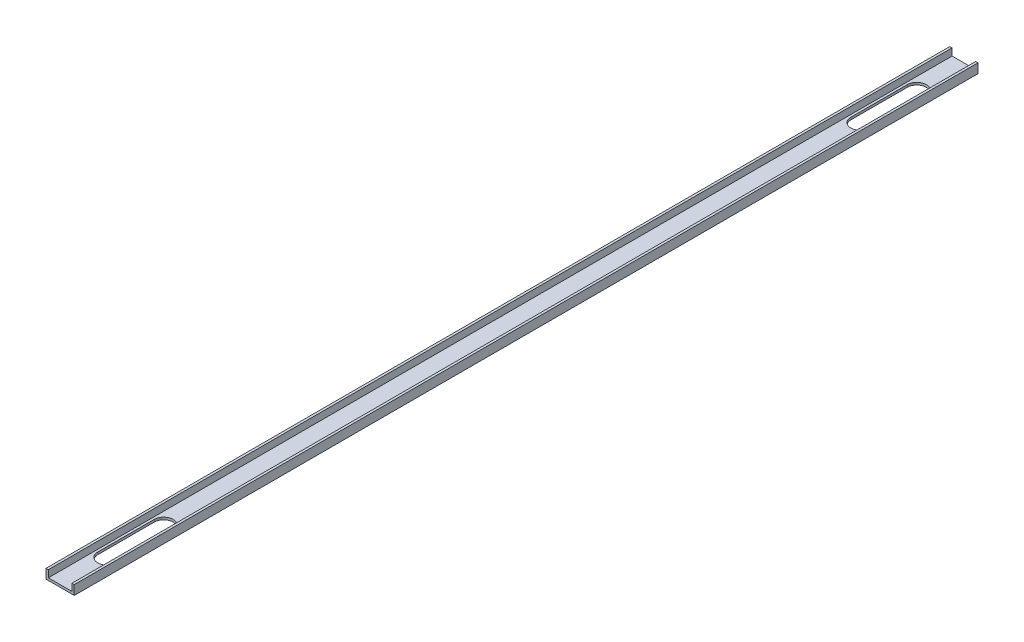
SolidWorks part; units mm, degrees
ref_plane "Front" through (0, 0, 0) normal (0, 0, 1) x (1, 0, 0)
ref_plane "Top" through (0, 0, 0) normal (0, 1, 0) x (1, 0, 0)
ref_plane "Right" through (0, 0, 0) normal (1, 0, 0) x (0, 0, -1)
sketch "Sketch1" plane through (0, 0, 0) normal (0, 0, 1) x (1, 0, 0)
  line L0 (3.175, 3.175) -> (3.175, 12.7)
  line L1 (0, 0) -> (38.1, 0)
  line L2 (0, 0) -> (0, 12.7)
  line L4 (38.1, 0) -> (38.1, 12.7)
  line L5 (3.175, 3.175) -> (34.925, 3.175)
  line L6 (34.925, 3.175) -> (34.925, 12.7)
  line L7 (0, 12.7) -> (3.175, 12.7)
  line L8 (38.1, 12.7) -> (34.925, 12.7)
  dimension "D1" = 12.7
  dimension "D2" = 38.1
  dimension "D3" = 3.175
extrude "f" add sketch "Sketch1" along normal blind 1219.2
sketch "Sketch2" plane through (0, 3.175, 0) normal (0, 1, 0) x (1, 0, 0)
  line L0 (3.175, -1117.6) -> (34.925, -1117.6) construction
  line L1 (3.175, -1219.2) -> (3.175, 0) construction
  line L2 (34.925, -1219.2) -> (34.925, 0) construction
  line L3 (19.05, -1155.7) -> (19.05, -1079.5) construction
  line L4 (6.35, -1155.7) -> (6.35, -1079.5)
  line L5 (31.75, -1155.7) -> (31.75, -1079.5)
  line L6 (34.925, -1219.2) -> (3.175, -1219.2) construction
  arc A0 (6.35, -1155.7) -> (31.75, -1155.7) centre (19.05, -1155.7) ccw
  arc A1 (31.75, -1079.5) -> (6.35, -1079.5) centre (19.05, -1079.5) ccw
  point P8 (19.05, -1117.6)
  dimension "D1" = 76.2
  dimension "D2" = 101.6
extrude "Cut-Extrude1" cut sketch "Sketch2" against normal up to next
ref_plane "Plane1" through (0, 0, 609.6) normal (0, 0, 1) x (1, 0, 0)
mirror "Mirror1" about plane through (0, 0, 609.6) normal (0, 0, 1) of "Cut-Extrude1"
